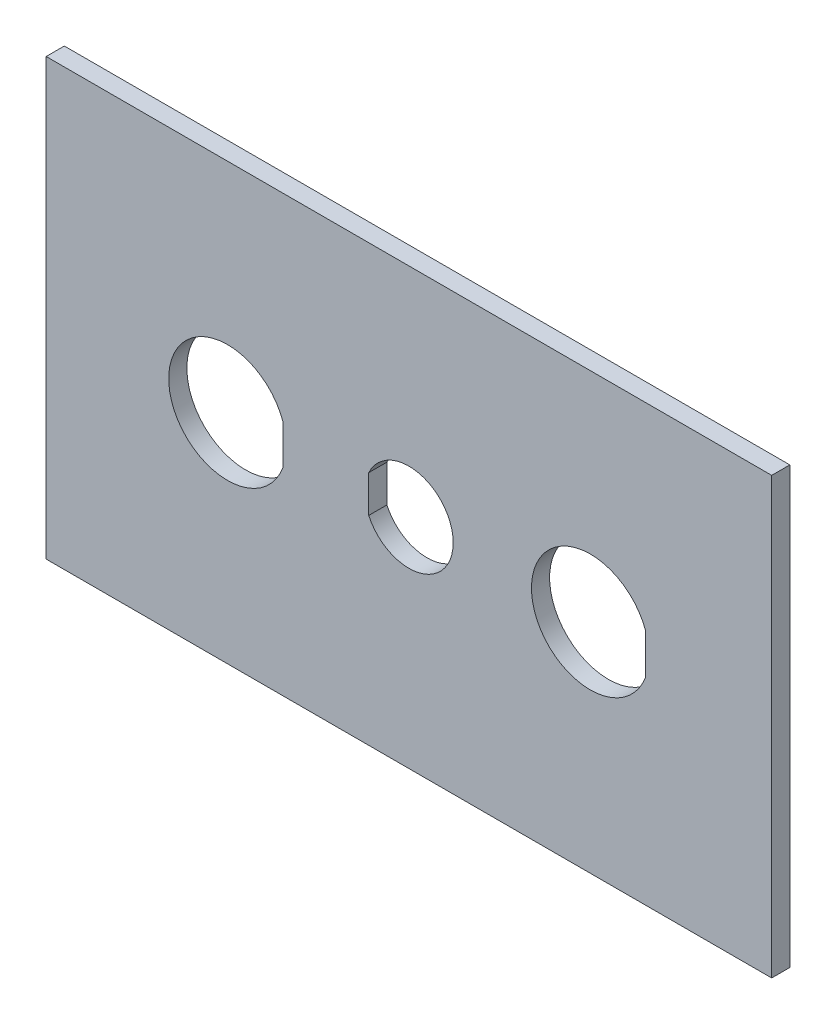
SolidWorks part; units mm, degrees
ref_plane "Front Plane" through (0, 0, 0) normal (0, 0, 1) x (1, 0, 0)
ref_plane "Top Plane" through (0, 0, 0) normal (0, 1, 0) x (1, 0, 0)
ref_plane "Right Plane" through (0, 0, 0) normal (1, 0, 0) x (0, 0, -1)
sketch "Sketch1" plane through (0, 0, 0) normal (0, 0, 1) x (1, 0, 0)
  line L1 (-63.5, 38.1) -> (63.5, 38.1)
  line L2 (-63.5, 38.1) -> (-63.5, -38.1)
  line L3 (-63.5, -38.1) -> (63.5, -38.1)
  line L4 (63.5, 38.1) -> (63.5, -38.1)
  line L5 (-63.5, 38.1) -> (63.5, -38.1) construction
  line L6 (-63.5, -38.1) -> (63.5, 38.1) construction
  line L8 (-63.5, 0) -> (63.5, 0) construction
  line L9 (-7.0358, 3.2425) -> (-7.0358, -3.2425)
  line L10 (41.45, 3.4641) -> (41.45, -3.4641)
  line L11 (-22.05, 3.4641) -> (-22.05, -3.4641)
  arc A2 (-7.0358, -3.2425) -> (-7.0358, 3.2425) centre (0, 0) ccw
  arc A4 (41.45, 3.4641) -> (41.45, -3.4641) centre (31.75, 0) ccw
  arc A5 (-22.05, 3.4641) -> (-22.05, -3.4641) centre (-31.75, 0) ccw
  point P0 (0, 0)
  point P9 (21.45, 0)
  point P12 (7.747, 0)
  dimension "D3" = 15.494
  dimension "D6" = 20.6
  dimension "D1" = 127
  dimension "D2" = 76.2
  dimension "D4" = 14.7828
  dimension "D5" = 0
  dimension "D7" = 20
  dimension "D8" = 31.75
  dimension "D9" = 31.75
extrude "Boss-Extrude1" add sketch "Sketch1" along normal blind 3.175
